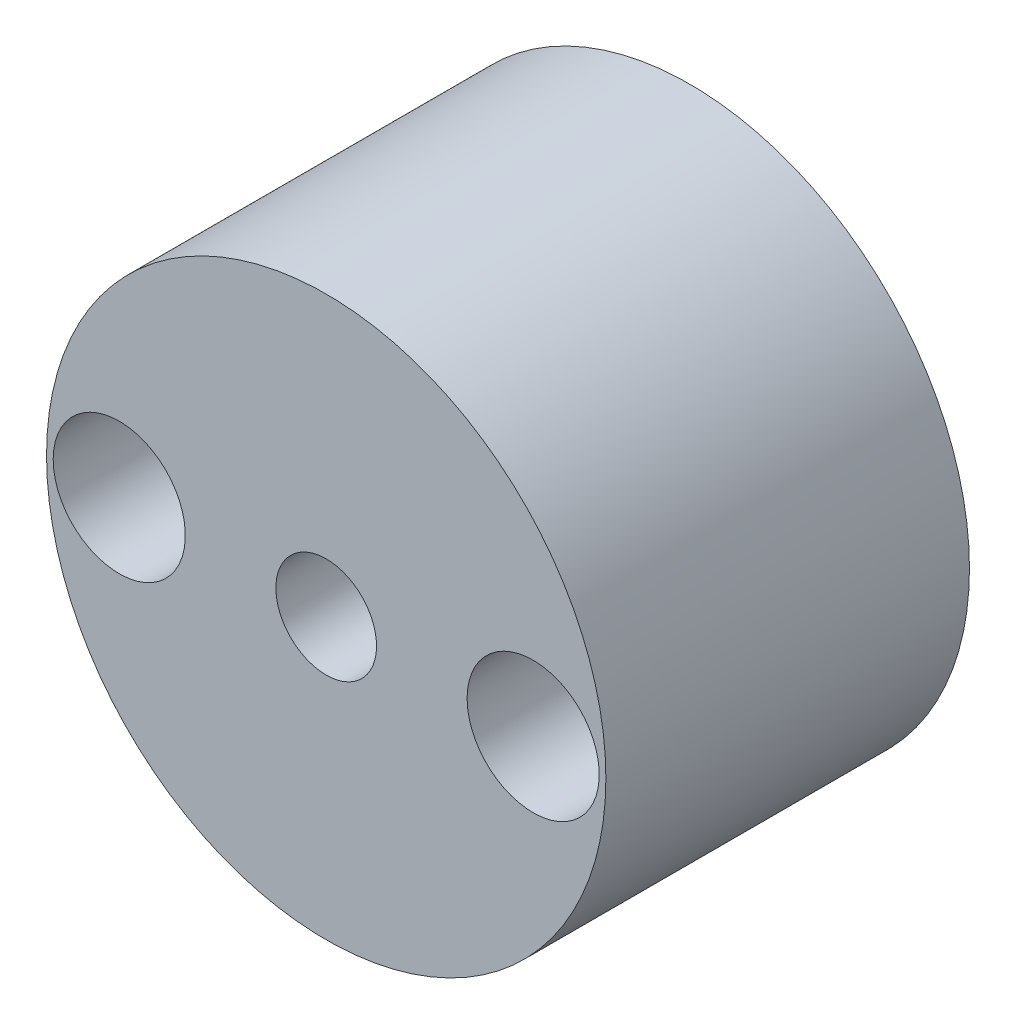
SolidWorks part; units mm, degrees
ref_plane "Front Plane" through (0, 0, 0) normal (0, 0, 1) x (1, 0, 0)
ref_plane "Top Plane" through (0, 0, 0) normal (0, 1, 0) x (1, 0, 0)
ref_plane "Right Plane" through (0, 0, 0) normal (1, 0, 0) x (0, 0, -1)
sketch "Sketch1" plane through (0, 0, 0) normal (0, 0, 1) x (1, 0, 0)
  line L0 (-2.413, 0) -> (2.413, 0) construction
  line L1 (-2.413, -2.54) -> (0, 0) construction
  line L2 (-2.413, -2.54) -> (-2.413, 2.54)
  line L3 (-2.413, 2.54) -> (2.413, 2.54) construction
  line L4 (2.413, -2.54) -> (2.413, 2.54)
  line L5 (0, 0) -> (2.413, 2.54) construction
  line L6 (-2.413, 2.54) -> (0, 0) construction
  line L7 (0, 0) -> (2.413, -2.54) construction
  line L8 (-2.413, -2.54) -> (2.413, -2.54) construction
  arc A0 (-2.413, 2.54) -> (2.413, 2.54) centre (0, 0) cw
  arc A1 (-2.413, -2.54) -> (2.413, -2.54) centre (0, 0) ccw
  circle A2 centre (0, 0) radius 6.35
  point P0 (0, 0)
  dimension "D3" = 12.7
  dimension "D1" = 4.826
  dimension "D2" = 2.54
extrude "Boss-Extrude1" add sketch "Sketch1" along normal blind 5.08
sketch "Sketch2" plane through (0, 0, 5.08) normal (0, 0, 1) x (1, 0, 0)
  circle A0 centre (0, 0) radius 1.143
  circle A1 centre (0, 0) radius 6.35
  dimension "D1" = 12.7
  dimension "D2" = 2.286
extrude "Boss-Extrude2" add sketch "Sketch2" along normal blind 3.175
hole_wizard "Ø3.0mm Dowel Hole1" positions "Sketch7" profile "Sketch6" hole size "Ø3.0" standard "ISO" end condition through all
sketch "Sketch7" plane through (0, 0, 0) normal (0, 0, -1) x (-1, 0, 0)
  line L0 (-6.35, 0) -> (6.35, 0) construction
  line L1 (-2.413, -2.54) -> (-2.413, 2.54) construction
  line L2 (2.413, 2.54) -> (2.413, -2.54) construction
  circle A0 centre (0, 0) radius 6.35 construction
  point P0 (-4.699, 0)
  point P2 (4.699, 0)
  dimension "D1" = 2.286
  dimension "D2" = 2.286
sketch "Sketch6" plane through (4.699, 0, 0) normal (1, 0, 0) x (0, 1, 0)
  line L0 (0, 0) -> (0, 8.255)
  line L1 (0, 8.255) -> (1.5, 8.255)
  line L2 (1.5, 8.255) -> (1.5, 0)
  line L5 (1.5, 0) -> (0, 0)
  line L11 (0, -6.35) -> (0, 107.95) construction
  dimension "Thru Hole Dia." = 3
  dimension "Thru Hole Depth" = 8.255
